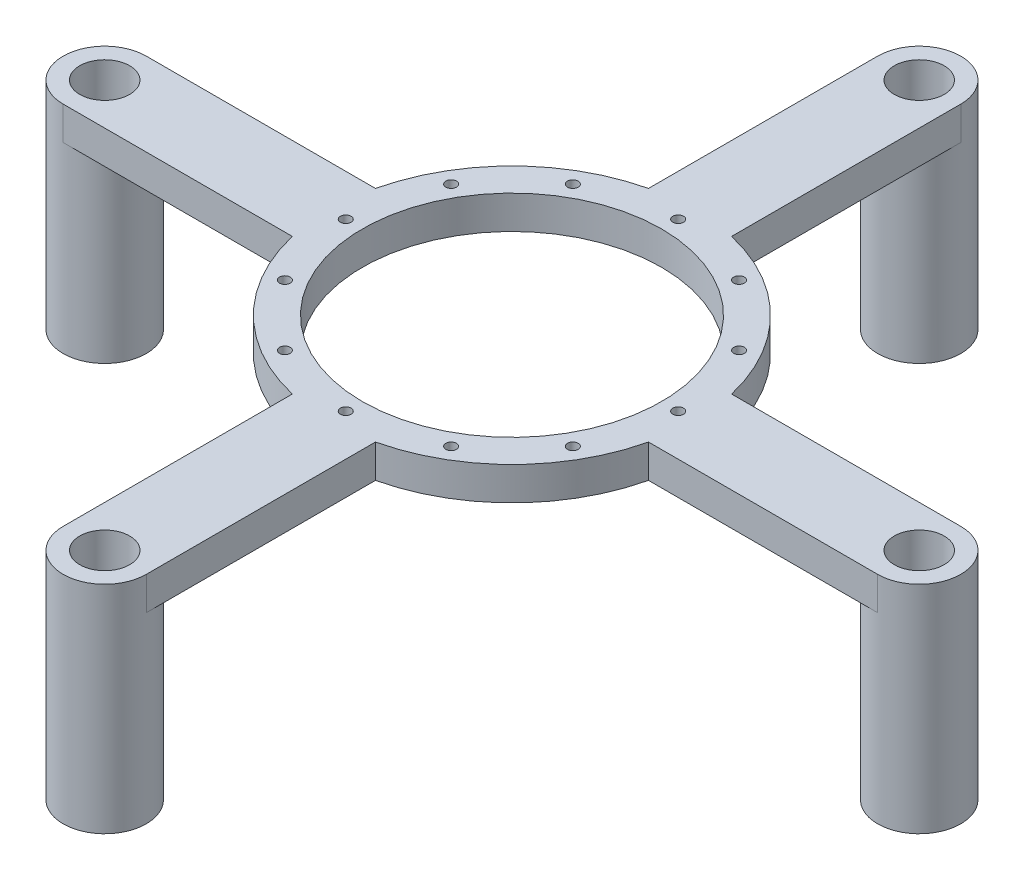
SolidWorks part; units mm, degrees
note: The reader was unsure of these and kept them because the rebuilt part matched: shared geometry of "Sketch1<3>", "Sketch1<5>".
ref_plane "Front Plane" through (0, 0, 0) normal (0, 0, 1) x (1, 0, 0)
ref_plane "Top Plane" through (0, 0, 0) normal (0, 1, 0) x (1, 0, 0)
ref_plane "Right Plane" through (0, 0, 0) normal (1, 0, 0) x (0, 0, -1)
sketch "Sketch1" plane through (0, 0, 0) normal (0, 1, 0) x (1, 0, 0)
  line L0 (-5842.1326, 0) -> (5000.2929, 0) construction
  line L1 (-122.5, -122.5) -> (122.5, -122.5) construction
  line L2 (-122.5, -122.5) -> (-122.5, 122.5) construction
  line L3 (-122.5, 122.5) -> (122.5, 122.5) construction
  line L4 (122.5, -122.5) -> (122.5, 122.5) construction
  line L5 (-122.5, -122.5) -> (122.5, 122.5) construction
  line L6 (-122.5, 122.5) -> (122.5, -122.5) construction
  line L7 (0, 4148.0375) -> (0, -3692.6273) construction
  line L8 (122.5, 12.5) -> (53.5607, 12.5)
  line L9 (122.5, -12.5) -> (53.5607, -12.5)
  line L10 (12.5, -122.5) -> (12.5, -53.5607)
  line L11 (-12.5, -122.5) -> (-12.5, -53.5607)
  line L12 (-122.5, -12.5) -> (-53.5607, -12.5)
  line L13 (-122.5, 12.5) -> (-53.5607, 12.5)
  line L14 (-12.5, 122.5) -> (-12.5, 53.5607)
  line L15 (12.5, 122.5) -> (12.5, 53.5607)
  circle A0 centre (122.5, 0) radius 1.6
  circle A1 centre (122.5, 0) radius 7.5
  circle A8 centre (122.5, 0) radius 12.5
  circle A9 centre (0, 0) radius 55
  circle A10 centre (0, 0) radius 45
  circle A11 centre (0, 50) radius 1.6
  circle A12 centre (25, 43.3013) radius 1.6
  circle A13 centre (43.3013, 25) radius 1.6
  circle A14 centre (50, 0) radius 1.6
  circle A15 centre (43.3013, -25) radius 1.6
  circle A16 centre (25, -43.3013) radius 1.6
  circle A17 centre (0, -50) radius 1.6
  circle A18 centre (-25, -43.3013) radius 1.6
  circle A19 centre (-43.3013, -25) radius 1.6
  circle A20 centre (-50, 0) radius 1.6
  circle A21 centre (-43.3013, 25) radius 1.6
  circle A22 centre (-25, 43.3013) radius 1.6
  circle A23 centre (0, -122.5) radius 12.5
  circle A24 centre (0, -122.5) radius 7.5
  circle A25 centre (0, -122.5) radius 1.6
  circle A26 centre (-122.5, 0) radius 12.5
  circle A27 centre (-122.5, 0) radius 7.5
  circle A28 centre (-122.5, 0) radius 1.6
  circle A29 centre (0, 122.5) radius 12.5
  circle A30 centre (0, 122.5) radius 7.5
  circle A31 centre (0, 122.5) radius 1.6
  point P0 (0, 0)
  point P25 (0, 0)
  point P48 (0, 0)
  point P74 (0, 0)
  dimension "D3" = 3.2
  dimension "D4" = 15
  dimension "D6" = 25
  dimension "D5" = 110
  dimension "D7" = 90
  dimension "D8" = 3.2
  dimension "D1" = 245
  dimension "D2" = 245
  dimension "D9" = 50
  dimension "D10" = 12
  dimension "D11" = 4
extrude "Boss-Extrude1" add sketch "Sketch1" along normal blind 65 contours A9 L9 A8 L8 | A8 A1 | A1 A0 | A29 L14 A9 L15 | A30 A31 | A29 A30 | A27 A28 | A26 A27 | A26 L12 A9 L13 | A24 A25 | A23 A24 | A23 L10 A9 L11 | A9 A22 A21 A20 A19 A18 A17 A16 A15 A14 A13 A12 A11 A10
extrude "Boss-Extrude2" add sketch "Sketch1<3>" along normal blind 3.2 contours A24 A25 | A1 A0 | A30 A31 | A27 A28
sketch "Sketch1<3>" plane through (0, 0, 0) normal (0, 1, 0) x (1, 0, 0) same geometry as "Sketch1"
extrude "Cut-Extrude2" cut sketch "Sketch1<5>" along normal blind 55 contours A26 L12 A9 L13 | A23 L10 A9 L11 | A9 L9 A8 L8 | A29 L14 A9 L15 | A9 A22 A21 A20 A19 A18 A17 A16 A15 A14 A13 A12 A11 A10
sketch "Sketch1<5>" plane through (0, 0, 0) normal (0, 1, 0) x (1, 0, 0) same geometry as "Sketch1"
